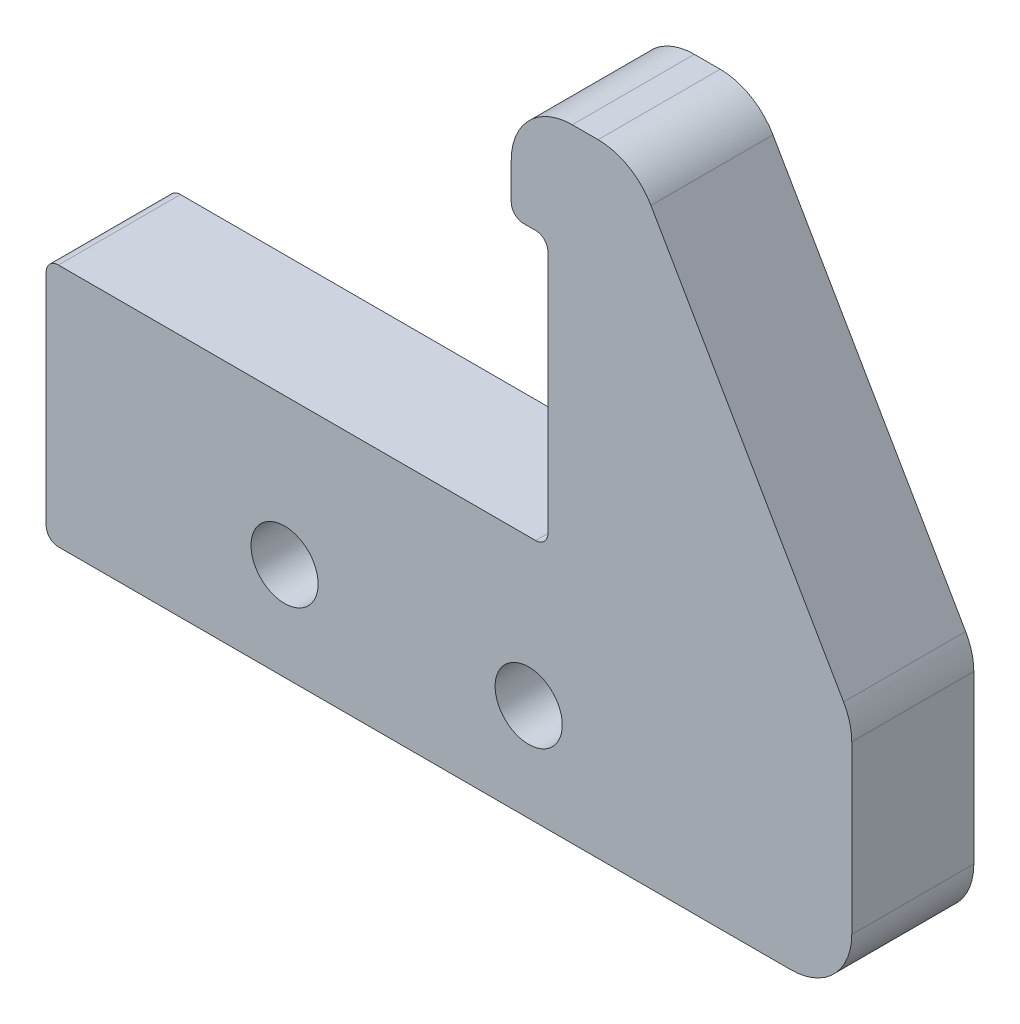
SolidWorks part; units mm, degrees
ref_plane "Front Plane" through (0, 0, 0) normal (0, 0, 1) x (1, 0, 0)
ref_plane "Top Plane" through (0, 0, 0) normal (0, 1, 0) x (1, 0, 0)
ref_plane "Right Plane" through (0, 0, 0) normal (1, 0, 0) x (0, 0, -1)
sketch "Sketch1" plane through (0, 0, 0) normal (0, 0, 1) x (1, 0, 0)
  line L3 (-66, 20) -> (-24.8979, 20)
  line L4 (-24.8979, 20) -> (-24.8979, 42)
  line L5 (-24.8979, 42) -> (-27.8979, 42)
  line L6 (-27.8979, 42) -> (-27.8979, 51)
  line L7 (-27.8979, 51) -> (-17.8979, 51)
  line L8 (-17.8979, 51) -> (0, 20)
  line L9 (0, 20) -> (0, 0)
  line L10 (0, 0) -> (-66, 0)
  line L11 (-66, 20) -> (-66, 0)
  point P1 (0, 0)
  dimension "D1" = 66
  dimension "D2" = 10
  dimension "D3" = 9
  dimension "D4" = 3
  dimension "D5" = 22
  dimension "D6" = 20
  dimension "D7" = 30
extrude "Boss-Extrude1" add sketch "Sketch1" along normal blind 10
fillet "Fillet1" radius 5 4 edges at (0, 0, 5) (0, 20, 5) (-17.8979, 51, 5) (-27.8979, 51, 5)
fillet "Fillet2" radius 1 5 edges at (-24.8979, 20, 5) (-24.8979, 42, 5) (-27.8979, 42, 5) (-66, 0, 5) (-66, 20, 5)
hole_wizard "M5 Clearance Hole1" positions "Sketch2" profile "Sketch3" hole size "M5" standard "ISO" end condition through all
sketch "Sketch2" plane through (0, 0, 10) normal (0, 0, 1) x (1, 0, 0)
  line L0 (-65, 0) -> (-5, 0) construction
  line L1 (0, 5) -> (0, 18.6603) construction
  point P0 (-26.47, 8)
  point P2 (-46.47, 8)
  point P7 (0, 0)
  dimension "D1" = 8
  dimension "D2" = 20
  dimension "D3" = 26.47
sketch "Sketch3" plane through (-26.47, 8, 10) normal (1, 0, 0) x (0, -1, 0)
  line L0 (0, 0) -> (0, 10)
  line L1 (0, 10) -> (2.75, 10)
  line L2 (2.75, 10) -> (2.75, 0)
  line L5 (2.75, 0) -> (0, 0)
  line L11 (0, -6.35) -> (0, 107.95) construction
  dimension "Thru Hole Dia." = 5.5
  dimension "Thru Hole Depth" = 10
